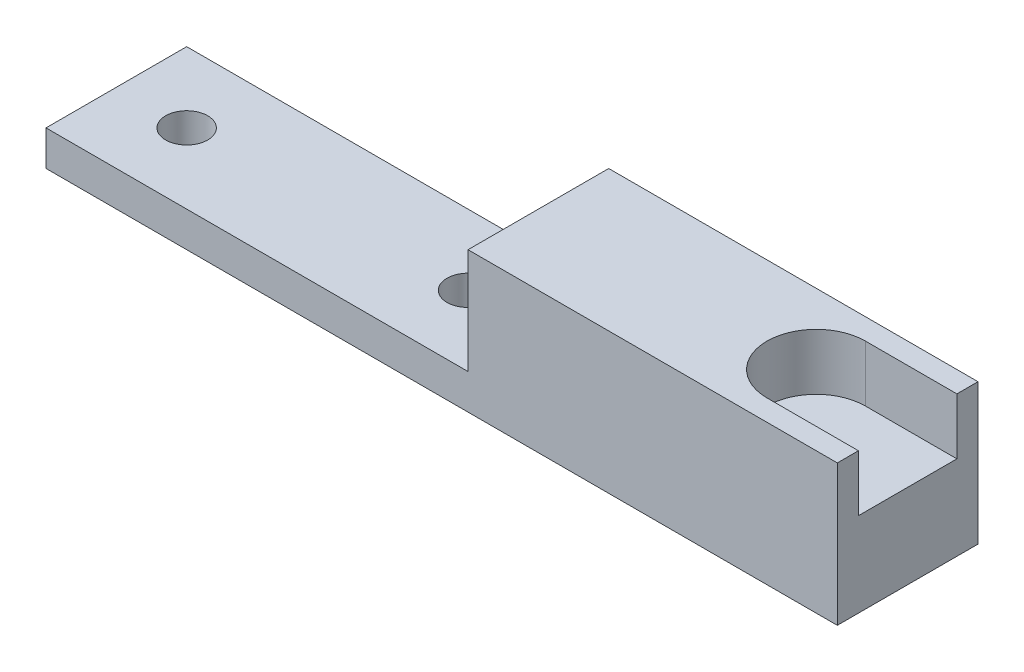
SolidWorks part; units mm, degrees
material "6061 Alloy"
ref_plane "Front Plane" through (0, 0, 0) normal (0, 0, 1) x (1, 0, 0)
ref_plane "Top Plane" through (0, 0, 0) normal (0, 1, 0) x (1, 0, 0)
ref_plane "Right Plane" through (0, 0, 0) normal (1, 0, 0) x (0, 0, -1)
sketch "Sketch1" plane through (0, 0, 0) normal (0, 1, 0) x (1, 0, 0)
  line L1 (-35.7187, -6.35) -> (35.7188, -6.35)
  line L2 (-35.7187, -6.35) -> (-35.7187, 6.35)
  line L3 (-35.7187, 6.35) -> (35.7188, 6.35)
  line L4 (35.7188, -6.35) -> (35.7188, 6.35)
  line L5 (-35.7187, -6.35) -> (35.7188, 6.35) construction
  line L6 (-35.7187, 6.35) -> (35.7188, -6.35) construction
  point P0 (0, 0)
  dimension "D1" = 12.7
  dimension "D2" = 71.4375
extrude "Boss-Extrude1" add sketch "Sketch1" along normal blind 12.7
hole_wizard "#6 Clearance Hole2" positions "Sketch4" profile "Sketch5" hole size "#6" standard "ANSI Inch" end condition through all
sketch "Sketch4" plane through (0, 0, 0) normal (0, -1, 0) x (-1, 0, 0)
  line L0 (35.7187, 6.35) -> (35.7187, -6.35) construction
  line L1 (-35.7188, 6.35) -> (35.7187, 6.35) construction
  point P0 (29.3687, 0)
  point P2 (3.9687, 0)
  dimension "D1" = 6.35
  dimension "D2" = 25.4
  dimension "D3" = 6.35
  dimension "D4" = 6.35
sketch "Sketch5" plane through (-29.3687, 0, 0) normal (1, 0, 0) x (0, 0, -1)
  line L0 (0, 0) -> (0, 12.7)
  line L1 (0, 12.7) -> (1.8986, 12.7)
  line L2 (1.8986, 12.7) -> (1.8986, 0)
  line L5 (1.8986, 0) -> (0, 0)
  line L11 (0, -6.35) -> (0, 107.95) construction
  dimension "Thru Hole Dia." = 3.7973
  dimension "Thru Hole Depth" = 12.7
sketch "Sketch6" plane through (0, 0, 6.35) normal (0, 0, 1) x (1, 0, 0)
  line L1 (-35.7187, 12.7) -> (2.3813, 12.7)
  line L2 (-35.7187, 12.7) -> (-35.7187, 3.175)
  line L3 (-35.7187, 3.175) -> (2.3813, 3.175)
  line L4 (2.3813, 12.7) -> (2.3813, 3.175)
  dimension "D1" = 38.1
  dimension "D2" = 9.525
extrude "Cut-Extrude1" cut sketch "Sketch6" against normal through all
sketch "Sketch8" plane through (0, 12.7, 0) normal (0, 1, 0) x (1, 0, 0)
  line L0 (35.7188, -6.35) -> (35.7188, 6.35) construction
  line L1 (23.0188, -4.445) -> (35.7188, -4.445)
  line L2 (23.0188, -4.445) -> (23.0188, 4.445)
  line L3 (23.0188, 4.445) -> (35.7188, 4.445)
  line L4 (35.7188, -4.445) -> (35.7188, 4.445)
  line L5 (23.0188, -4.445) -> (35.7188, 4.445) construction
  line L6 (23.0188, 4.445) -> (35.7188, -4.445) construction
  circle A1 centre (27.4638, 0) radius 4.445
  point P0 (29.3688, 0)
  point P7 (0, 0)
  line M6 (35.7188, -6.35) -> (35.7188, 6.35)
  dimension "D1" = 12.7
  dimension "D2" = 8.89
  dimension "D3" = 0
extrude "Cut-Extrude2" cut sketch "Sketch8" against normal blind 5.08 contours A1 | A1 L1 L3 M6 region at (33.2335, 12.7, 0) region at (27.4638, 12.7, 0)
